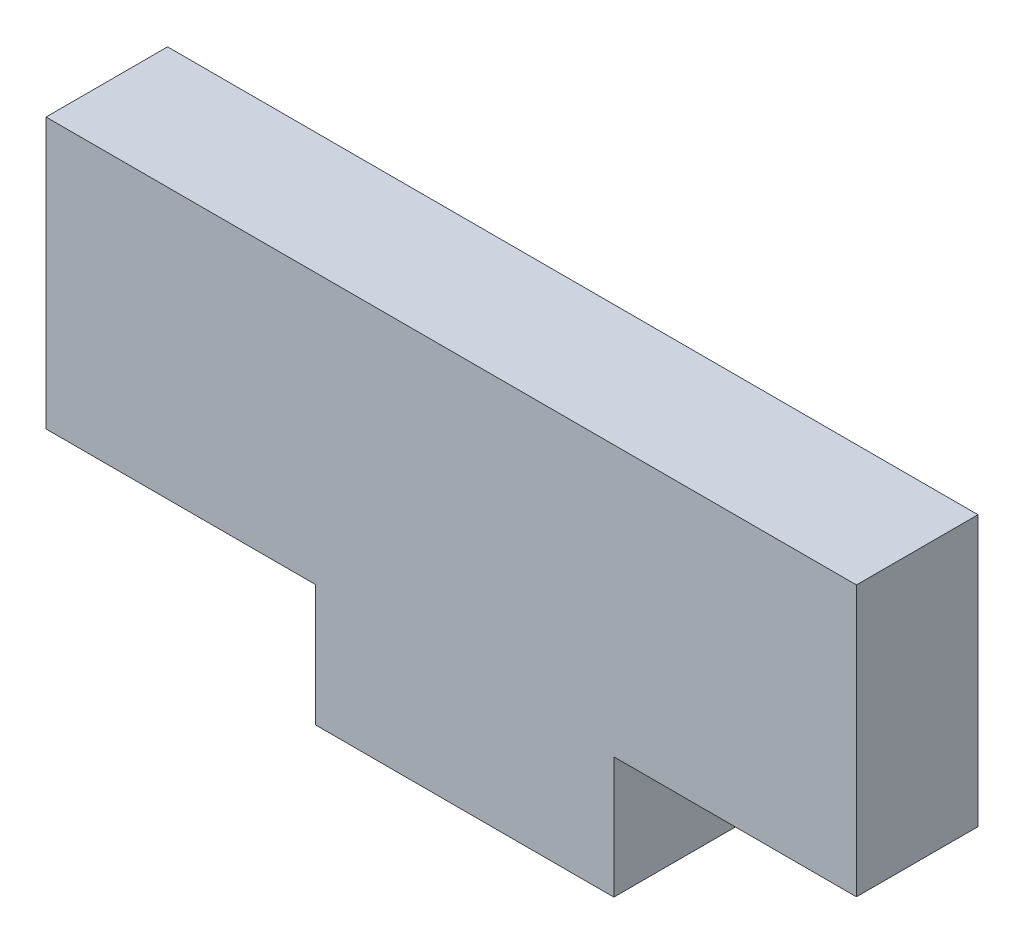
SolidWorks part; units mm, degrees
ref_plane "Front Plane" through (0, 0, 0) normal (0, 0, 1) x (1, 0, 0)
ref_plane "Top Plane" through (0, 0, 0) normal (0, 1, 0) x (1, 0, 0)
ref_plane "Right Plane" through (0, 0, 0) normal (1, 0, 0) x (0, 0, -1)
sketch "Sketch1" plane through (0, 0, 0) normal (0, 0, 1) x (1, 0, 0)
  line L0 (21.0202, 0) -> (30, 0)
  line L1 (0, 0) -> (9.9773, 0)
  line L2 (0, 0) -> (0, 10)
  line L3 (0, 10) -> (30, 10)
  line L4 (30, 0) -> (30, 10)
  line L6 (9.9773, 0) -> (9.9773, -4.5)
  line L7 (9.9773, -4.5) -> (21.0202, -4.5)
  line L8 (21.0202, 0) -> (21.0202, -4.5)
  dimension "D1" = 10
  dimension "D2" = 30
  dimension "D3" = 4.5
extrude "Boss-Extrude1" add sketch "Sketch1" along normal blind 4.5
equation "\"D3@Sketch1\" = \"mdf@fmv1.assembly\""
equation "\"D1@Boss-Extrude1\"=\"mdf@fmv1.assembly\""
